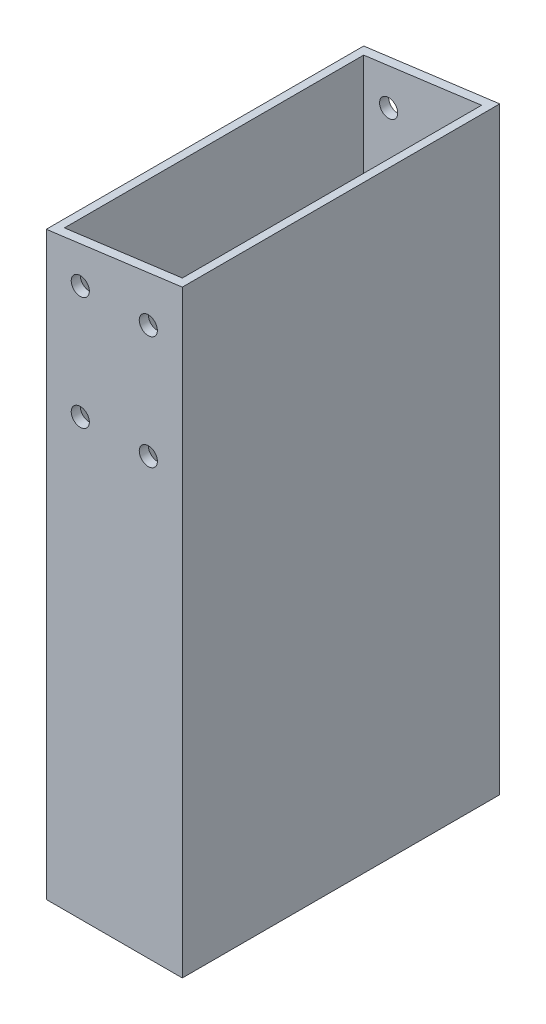
SolidWorks part; units mm, degrees
ref_plane "前视基准面" through (0, 0, 0) normal (0, 0, 1) x (1, 0, 0)
ref_plane "上视基准面" through (0, 0, 0) normal (0, 1, 0) x (1, 0, 0)
ref_plane "右视基准面" through (0, 0, 0) normal (1, 0, 0) x (0, 0, -1)
other "Configuration Table"
sketch "草图1" plane through (0, 0, 0) normal (0, 0, 1) x (1, 0, 0)
  line L1 (15, -375) -> (-15, -375)
  line L2 (15, -375) -> (15, 375)
  line L3 (15, 375) -> (-15, 375)
  line L4 (-15, -375) -> (-15, 375)
  line L5 (15, -375) -> (-15, 375) construction
  line L6 (15, 375) -> (-15, -375) construction
  circle A0 centre (-7.5, 363.9688) radius 2
  circle A2 centre (7.5, 363.9688) radius 2
  circle A3 centre (-7.5, 338.9688) radius 2
  circle A4 centre (7.5, 338.9688) radius 2
  circle A5 centre (-7.5, -312.8679) radius 2
  circle A6 centre (7.5, -312.8679) radius 2
  circle A7 centre (-7.5, -337.8679) radius 2
  circle A8 centre (7.5, -337.8679) radius 2
  point P0 (0, 0)
  dimension "D1" = 30
  dimension "D2" = 750
extrude "凸台-拉伸2" add sketch "草图1" along normal blind 70
sketch "草图2" plane through (0, -375, 0) normal (0, -1, 0) x (1, 0, 0)
  line L0 (-15, 70) -> (-15, 0) construction
  line L1 (-13, 68) -> (13, 68)
  line L2 (-13, 68) -> (-13, 2)
  line L3 (-13, 2) -> (13, 2)
  line L4 (13, 68) -> (13, 2)
  line L5 (-13, 68) -> (13, 2) construction
  line L6 (-13, 2) -> (13, 68) construction
  line L7 (-15, 70) -> (15, 70) construction
  line L8 (15, 70) -> (15, 0) construction
  line L9 (-15, 0) -> (15, 0) construction
  point P0 (0, 35)
  dimension "D1" = 2
  dimension "D2" = 2
  dimension "D3" = 2
  dimension "D4" = 2
extrude "切除-拉伸3" cut sketch "草图2" against normal through all contours L2 L1 L4 L3
sketch "草图3" plane through (0, 0, 70) normal (0, 0, 1) x (1, 0, 0)
  line L0 (15, 375) -> (-15, 371.0504)
  line L1 (-15, 375) -> (-15, -375) construction
  line L2 (15, -375) -> (15, 375) construction
  line L3 (15, -347.1) -> (-15, -343.1504)
  line L4 (-15, -343.1504) -> (-15, -376.6872)
  line L5 (-15, -376.6872) -> (15, -376.6872)
  line L6 (15, -376.6872) -> (15, -347.1)
  line L7 (-15, 371.0504) -> (-15, 377.0408)
  line L8 (-15, 377.0408) -> (15, 377.0408)
  line L9 (15, 377.0408) -> (15, 375)
  line M2 (-15, 375) -> (-15, -375)
  line M3 (-15, -375) -> (15, -375)
  line M4 (15, -375) -> (15, 375)
  dimension "D1" = 82.5
  dimension "D2" = 82.5
  dimension "D3" = 722.1
extrude "切除-拉伸4" cut sketch "草图3" against normal through all contours L3 M4 M2 M3 | L9 L0 L7 L8 region at (-0.3305, -360.0408, 70)
sketch "草图4" plane through (0, 0, 0) normal (0, 0, -1) x (-1, 0, 0)
  line L0 (-15, 243.0504) -> (15, 243.0504)
  line L1 (-15, -347.1) -> (-15, 375) construction
  line L2 (15, 371.0504) -> (15, -343.1504) construction
  line L3 (-15, 243.0504) -> (-15, -679.8701)
  line L4 (-15, -679.8701) -> (15, -679.8701)
  line L5 (15, -679.8701) -> (15, 243.0504)
  dimension "D1" = 128
extrude "切除-拉伸5" cut sketch "草图4" against normal through all
